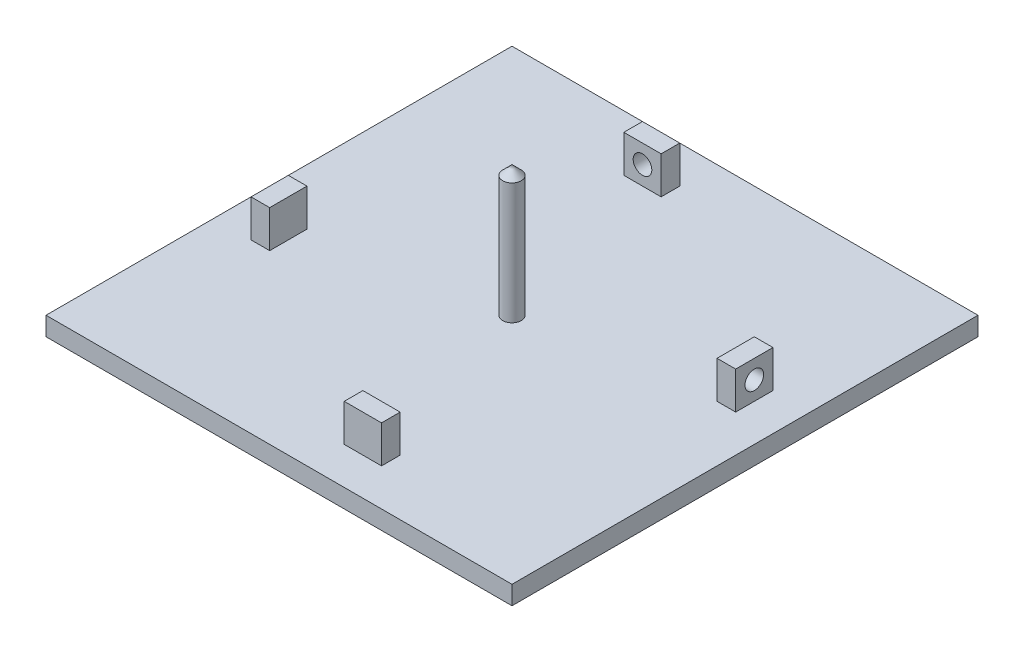
SolidWorks part; units mm, degrees
ref_plane "Front Plane" through (0, 0, 0) normal (0, 0, 1) x (1, 0, 0)
ref_plane "Top Plane" through (0, 0, 0) normal (0, 1, 0) x (1, 0, 0)
ref_plane "Right Plane" through (0, 0, 0) normal (1, 0, 0) x (0, 0, -1)
sketch "Sketch1" plane through (0, 0, 0) normal (0, 1, 0) x (1, 0, 0)
  line L0 (210, 70) -> (190, 70)
  line L1 (-250, -250) -> (250, -250)
  line L2 (-250, -250) -> (-250, 250)
  line L3 (-250, 250) -> (250, 250)
  line L4 (250, -250) -> (250, 250)
  line L5 (-250, -250) -> (250, 250) construction
  line L6 (-250, 250) -> (250, -250) construction
  line L7 (-200, 200) -> (200, 200) construction
  line L8 (-200, 200) -> (-200, -200) construction
  line L9 (-200, -200) -> (200, -200) construction
  line L10 (200, 200) -> (200, -200) construction
  line L11 (-70, 210) -> (-30, 210)
  line L12 (-70, 210) -> (-70, 190)
  line L13 (-70, 190) -> (-30, 190)
  line L14 (-30, 210) -> (-30, 190)
  line L15 (210, 70) -> (210, 30)
  line L16 (210, 30) -> (190, 30)
  line L17 (190, 70) -> (190, 30)
  line L18 (70, -210) -> (70, -190)
  line L19 (70, -210) -> (30, -210)
  line L20 (30, -210) -> (30, -190)
  line L21 (70, -190) -> (30, -190)
  line L22 (-210, -70) -> (-190, -70)
  line L23 (-210, -70) -> (-210, -30)
  line L24 (-210, -30) -> (-190, -30)
  line L25 (-190, -70) -> (-190, -30)
  line L26 (-50, 210) -> (-50, 190) construction
  point P0 (0, 0)
  point P10 (200, 0)
  point P11 (0, 200)
  point P16 (-30, 200)
  point P20 (-190, -30)
  point P33 (0, 0)
  point P34 (-70, 190)
  dimension "D1" = 500
  dimension "D2" = 40
  dimension "D3" = 20
  dimension "D4" = 400
  dimension "D6" = 50
  dimension "D5" = 4
extrude "Boss-Extrude1" add sketch "Sketch1" against normal blind 20 contours L2 L3 L4 L1
extrude "Boss-Extrude2" add sketch "Sketch1<3>" along normal blind 40 contours L22 L25 L24 L23 | L14 L11 L12 L13 | L0 L17 L16 L15 | L18 L21 L20 L19 region at (200, 0, -50) region at (-50, 0, -200) region at (50, 0, 200) region at (-200, 0, 50)
sketch "Sketch1<3>" plane through (0, 0, 0) normal (0, 1, 0) x (1, 0, 0) same geometry as "Sketch1"
sketch "Sketch5" plane through (0, 0, -210) normal (0, 0, -1) x (-1, 0, 0)
  line L0 (70, 40) -> (70, 0) construction
  line L1 (70, 40) -> (30, 40) construction
  circle A0 centre (50, 20) radius 10
  point P4 (70, 20)
  point P5 (0, 0)
  point P7 (48.4974, 20)
  point P10 (50, 40)
  dimension "D1" = 20
extrude "Cut-Extrude1" cut sketch "Sketch5" against normal through all
sketch "Sketch6" plane through (210, 0, 0) normal (1, 0, 0) x (0, 0, -1)
  line L0 (70, 40) -> (70, 0) construction
  line L1 (70, 40) -> (30, 40) construction
  circle A0 centre (50, 20) radius 10
  point P3 (0, 0)
  point P6 (70, 20)
  point P7 (46.9224, 20)
  point P10 (50, 40)
  dimension "D1" = 20
extrude "Cut-Extrude2" cut sketch "Sketch6" against normal through all
sketch "Sketch7" plane through (0, 0, 0) normal (1, 0, 0) x (0, 0, -1)
  line L0 (0, 0) -> (0, 140)
  line L1 (0, 140) -> (10, 130)
  line L2 (10, 130) -> (10, 0)
  line L3 (-250, 0) -> (250, 0) construction
  line L4 (10, 0) -> (0, 0)
  dimension "D1" = 10
  dimension "D2" = 140
  dimension "D3" = 10
revolve "Revolve1" add sketch "Sketch7" angle 360 about L0
